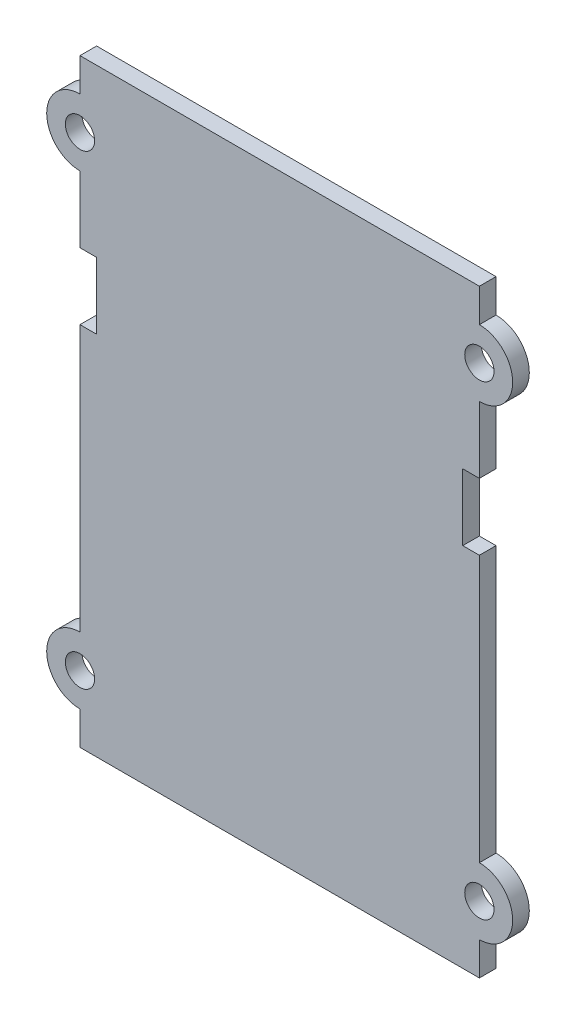
SolidWorks part; units mm, degrees
ref_plane "Front Plane" through (0, 0, 0) normal (0, 0, 1) x (1, 0, 0)
ref_plane "Top Plane" through (0, 0, 0) normal (0, 1, 0) x (1, 0, 0)
ref_plane "Right Plane" through (0, 0, 0) normal (1, 0, 0) x (0, 0, -1)
sketch "Sketch1" plane through (0, 0, 0) normal (0, 0, 1) x (1, 0, 0)
  line L0 (0, 105) -> (0, 110)
  line L1 (0, 0) -> (30, 0) construction
  line L2 (0, 20) -> (0, 25)
  line L3 (0, 110) -> (60, 110)
  line L4 (30, 20) -> (30, 110) construction
  line L5 (0, 85) -> (2.5, 85)
  line L6 (0, 35) -> (0, 75)
  line L7 (0, 75) -> (2.5, 75)
  line L8 (2.5, 85) -> (2.5, 75)
  line L9 (0, 85) -> (0, 95)
  line L10 (0, 20) -> (60, 20)
  line L11 (0, 0) -> (0, 20) construction
  line L12 (60, 85) -> (60, 95)
  line L13 (57.5, 85) -> (57.5, 75)
  line L14 (60, 75) -> (57.5, 75)
  line L15 (60, 35) -> (60, 75)
  line L16 (60, 85) -> (57.5, 85)
  line L17 (60, 20) -> (60, 25)
  line L18 (60, 105) -> (60, 110)
  arc A0 (0, 105) -> (0, 95) centre (0, 100) ccw
  circle A1 centre (0, 100) radius 2.2
  arc A2 (0, 35) -> (0, 25) centre (0, 30) ccw
  circle A3 centre (0, 30) radius 2.2
  circle A4 centre (60, 30) radius 2.2
  arc A5 (60, 35) -> (60, 25) centre (60, 30) cw
  circle A6 centre (60, 100) radius 2.2
  arc A7 (60, 105) -> (60, 95) centre (60, 100) cw
  dimension "D7" = 10
  dimension "D8" = 4.4
  dimension "D9" = 10
  dimension "D11" = 4.4
  dimension "D1" = 110
  dimension "D2" = 30
  dimension "D3" = 25
  dimension "D4" = 10
  dimension "D5" = 2.5
  dimension "D6" = 10
  dimension "D10" = 70
  dimension "D12" = 10
extrude "Boss-Extrude1" add sketch "Sketch1" along normal blind 2.5
